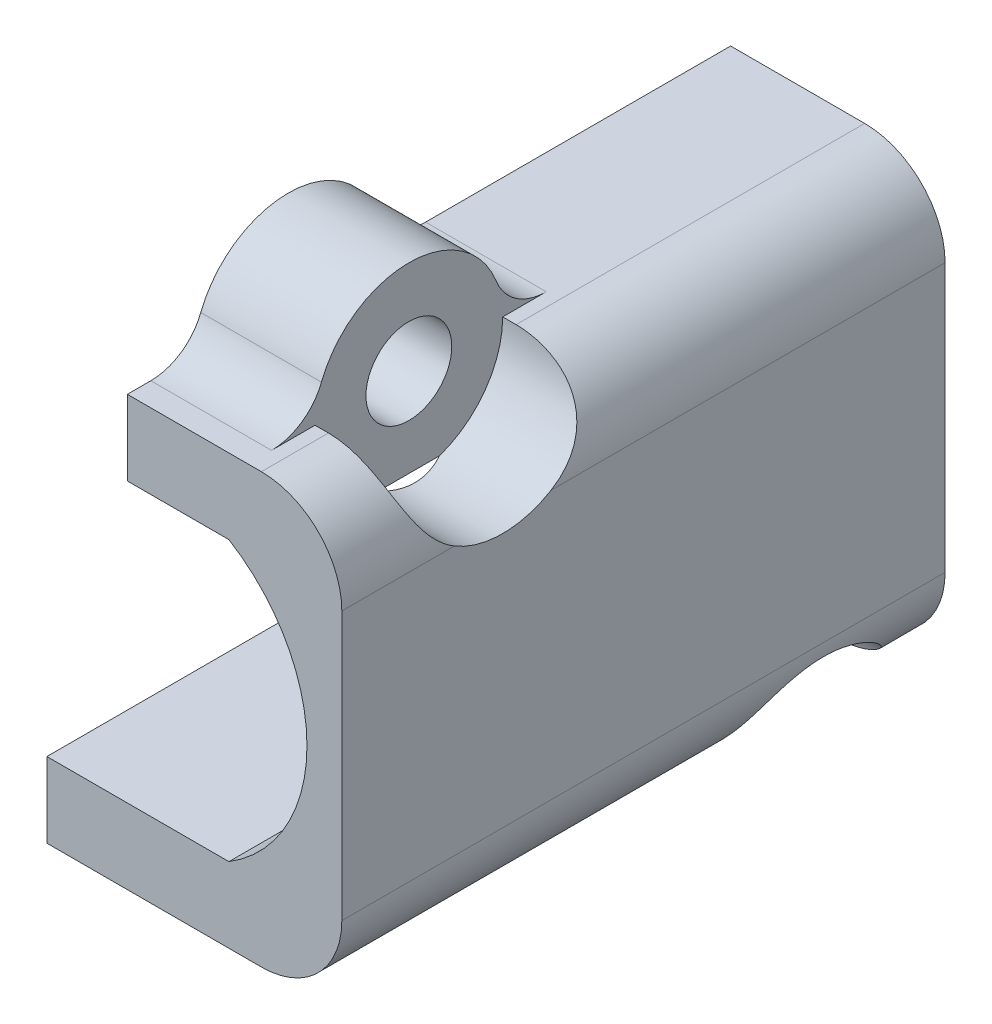
SolidWorks part; units mm, degrees
ref_plane "前视基准面" through (0, 0, 0) normal (0, 0, 1) x (1, 0, 0)
ref_plane "上视基准面" through (0, 0, 0) normal (0, 1, 0) x (1, 0, 0)
ref_plane "右视基准面" through (0, 0, 0) normal (1, 0, 0) x (0, 0, -1)
other "Configuration Table"
sketch "草图1" plane through (0, 0, 0) normal (0, 1, 0) x (1, 0, 0)
  line L1 (0, 0) -> (8, 0)
  line L2 (0, 0) -> (0, 20)
  line L3 (0, 20) -> (8, 20)
  line L4 (8, 0) -> (8, 20)
  line L5 (0, 0) -> (8, 20) construction
  line L6 (0, 20) -> (8, 0) construction
  point P4 (4, 10)
  dimension "D1" = 8
  dimension "D2" = 20
extrude "凸台-拉伸1" add sketch "草图1" along normal blind 16
sketch "草图2" plane through (0, 0, 0) normal (0, 0, 1) x (1, 0, 0)
  line L0 (0, 16) -> (0, 0) construction
  line L1 (0, 2.8) -> (6.8, 2.8)
  line L2 (0, 2.8) -> (0, 13.2)
  line L3 (0, 13.2) -> (6.8, 13.2)
  line L4 (6.8, 2.8) -> (6.8, 13.2)
  line L5 (0, 2.8) -> (6.8, 13.2) construction
  line L6 (0, 13.2) -> (6.8, 2.8) construction
  line L7 (8, 8) -> (3.4, 8) construction
  line L8 (8, 16) -> (8, 0) construction
  point P4 (3.4, 8)
  dimension "D1" = 6.8
  dimension "D2" = 10.4
extrude "切除-拉伸1" cut sketch "草图2" against normal up to next
sketch "草图3" plane through (0, 0, 0) normal (0, 0, 1) x (1, 0, 0)
  line L1 (0.6, 8) -> (8, 8) construction
  line L2 (8, 16) -> (8, 0) construction
  line L3 (3.789, 13.2) -> (6.8, 13.2)
  line L4 (6.8, 13.2) -> (0, 13.2) construction
  line L5 (6.8, 13.2) -> (6.8, 2.8)
  line L6 (6.8, 2.8) -> (3.789, 2.8)
  line L8 (0, 2.8) -> (6.8, 2.8) construction
  arc A0 (3.789, 2.8) -> (3.789, 13.2) centre (0.6, 8) ccw
  point P2 (-1.1854, 10)
  point P3 (3.789, 4.8)
  point P17 (0, 0)
  dimension "D1" = 12.2
  dimension "D2" = 6.2
extrude "凸台-拉伸3" add sketch "草图3" against normal offset from surface (10.8 mm away) 9.2 up to face at (3.7, 8, -20)
sketch "草图4" plane through (8, 0, 0) normal (1, 0, 0) x (0, 0, -1)
  line L0 (0, 8) -> (20, 8) construction
  line L1 (0, 16) -> (0, 0) construction
  line L2 (20, 16) -> (20, 0) construction
  circle A0 centre (4, 16) radius 1.6
  circle A1 centre (16, -1) radius 1.6
  dimension "D1" = 8
  dimension "D2" = 16
  dimension "D3" = 3.2
  dimension "D4" = 4
  dimension "D5" = 9
extrude "切除-拉伸2" cut sketch "草图4" against normal up to next
sketch "草图6" plane through (0, 0, 0) normal (-1, 0, 0) x (0, 0, 1)
  line L5 (-20, 0) -> (-17.249, 0)
  line L6 (-14.751, 0) -> (0, 0)
  line L7 (0, 0) -> (0, 2.8)
  line L8 (0, 2.8) -> (-20, 2.8)
  line L9 (-20, 2.8) -> (-20, 0)
  line L10 (-20, 0) -> (-17.249, 0)
  line L11 (-14.751, 0) -> (0, 0)
  line L12 (0, 0) -> (0, 2.8)
  line L13 (0, 2.8) -> (-20, 2.8)
  line L14 (-20, 2.8) -> (-20, 0)
  arc A1 (-14.751, 0) -> (-17.249, 0) centre (-16, -1) ccw
  arc A2 (-14.751, 0) -> (-17.249, 0) centre (-16, -1) ccw
  dimension "D1" = 0
extrude "凸台-拉伸5" add sketch "草图6" along normal blind 3
sketch "草图5" plane through (0, 0, 0) normal (-1, 0, 0) x (0, 0, 1)
  line L0 (-6.1, 13.2) -> (-1.9, 13.2)
  line L1 (-20, 13.2) -> (0, 13.2) construction
  circle A0 centre (-4, 16) radius 1.6
  arc A2 (-1.9, 13.2) -> (-6.1, 13.2) centre (-4, 16) ccw
  dimension "D2" = 7
extrude "凸台-拉伸4" add sketch "草图5" against normal blind 4.5
sketch "草图7" plane through (-3, 0, 0) normal (-1, 0, 0) x (0, 0, 1)
  circle A0 centre (-16, -1) radius 1.6
  circle A1 centre (-16, -1) radius 3.5
  dimension "D1" = 7
extrude "凸台-拉伸6" add sketch "草图7" against normal blind 3
sketch "草图8" plane through (0, 0, 0) normal (1, 0, 0) x (0, 0, -1)
  circle A0 centre (16, -1) radius 3.5
extrude "切除-拉伸3" cut sketch "草图8" along normal up to next
sketch "草图9" plane through (0, 0, -20) normal (0, 0, -1) x (-1, 0, 0)
  line L8 (-6.8, 2.8) -> (-6.8, 13.2)
  line L9 (-6.8, 13.2) -> (0, 13.2)
  line L10 (0, 13.2) -> (0, 16)
  line L11 (0, 16) -> (-8, 16)
  line L12 (-8, 16) -> (-8, 0)
  line L13 (-8, 0) -> (3, 0)
  line L14 (3, 0) -> (3, 2.8)
  line L15 (3, 2.8) -> (-6.8, 2.8)
  line L16 (-6.8, 2.8) -> (-6.8, 13.2)
  line L17 (-6.8, 13.2) -> (0, 13.2)
  line L18 (0, 13.2) -> (0, 16)
  line L19 (0, 16) -> (-8, 16)
  line L20 (-8, 16) -> (-8, 0)
  line L21 (-8, 0) -> (3, 0)
  line L22 (3, 0) -> (3, 2.8)
  line L23 (3, 2.8) -> (-6.8, 2.8)
  dimension "D1" = 0
extrude "凸台-拉伸7" add sketch "草图9" along normal blind 0.5
sketch "草图10" plane through (4.5, 0, 0) normal (1, 0, 0) x (0, 0, -1)
  circle A0 centre (4, 16) radius 3.5
extrude "切除-拉伸4" cut sketch "草图10" along normal up to next
sketch "草图11" plane through (0, 0, 0) normal (0, 0, 1) x (1, 0, 0)
  line L7 (0, 13.2) -> (3.789, 13.2)
  line L8 (3.789, 2.8) -> (-3, 2.8)
  line L9 (-3, 2.8) -> (-3, 0)
  line L10 (-3, 0) -> (8, 0)
  line L11 (8, 0) -> (8, 16)
  line L12 (8, 16) -> (0, 16)
  line L13 (0, 16) -> (0, 13.2)
  line L14 (0, 13.2) -> (3.789, 13.2)
  line L15 (3.789, 2.8) -> (-3, 2.8)
  line L16 (-3, 2.8) -> (-3, 0)
  line L17 (-3, 0) -> (8, 0)
  line L18 (8, 0) -> (8, 16)
  line L19 (8, 16) -> (0, 16)
  line L20 (0, 16) -> (0, 13.2)
  arc A1 (3.789, 2.8) -> (3.789, 13.2) centre (0.6, 8) ccw
  arc A2 (3.789, 2.8) -> (3.789, 13.2) centre (0.6, 8) ccw
  dimension "D1" = 0
extrude "凸台-拉伸8" add sketch "草图11" along normal blind 2
fillet "圆角1" radius 2 4 edges at (2.25, 16, -7.5) (2.25, 16, -0.5) (-1.5, 0, -12.6459) (-1.5, 0, -19.3541)
fillet "圆角2" radius 3 3 edges at (8, 16, 0.75) (8, 16, -14) (8, 0, -5.3229)
